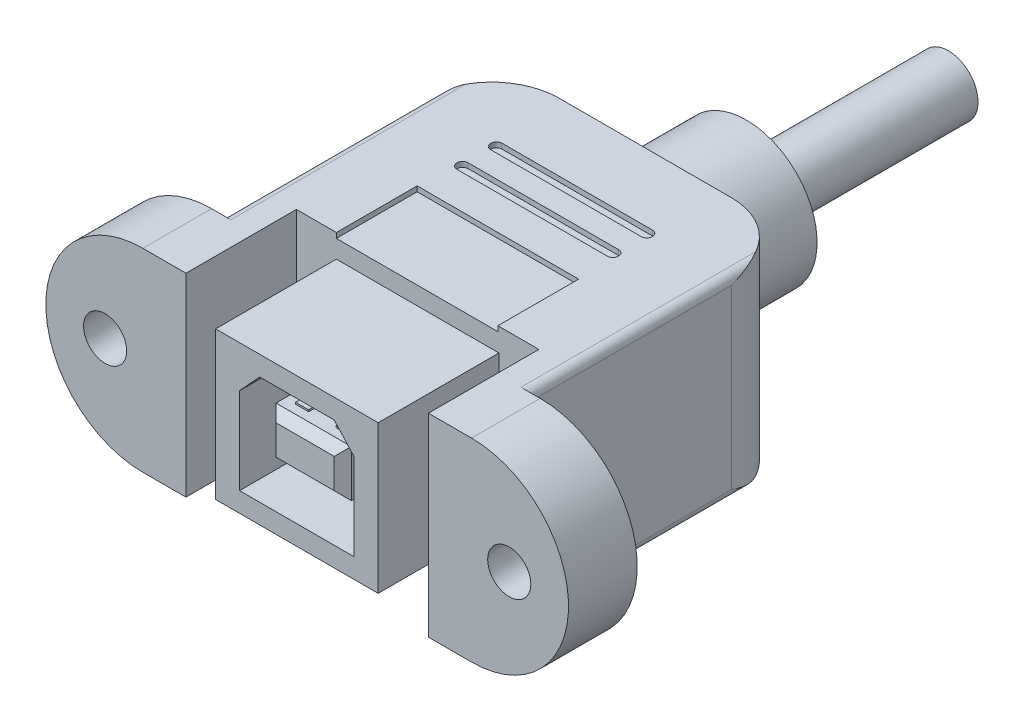
SolidWorks part; units mm, degrees
ref_plane "Front Plane" through (0, 0, 0) normal (0, 0, 1) x (1, 0, 0)
ref_plane "Top Plane" through (0, 0, 0) normal (0, 1, 0) x (1, 0, 0)
ref_plane "Right Plane" through (0, 0, 0) normal (1, 0, 0) x (0, 0, -1)
sketch "Sketch1" plane through (0, 0, 0) normal (0, 0, 1) x (1, 0, 0)
  line L0 (-19.4, 0) -> (-15, 0) construction
  line L1 (-12.2, -7.2) -> (12.2, -7.2)
  line L2 (-15, 0) -> (0, 0) construction
  line L3 (-12.2, 7.2) -> (12.2, 7.2)
  line L4 (0, 0) -> (15, 0) construction
  line L5 (0, 7.2) -> (0, 0) construction
  line L6 (15, 0) -> (19.4, 0) construction
  line L7 (0, 0) -> (0, -7.2) construction
  arc A0 (-12.2, -7.2) -> (-12.2, 7.2) centre (-12.2, 0) cw
  arc A1 (12.2, 7.2) -> (12.2, -7.2) centre (12.2, 0) cw
  circle A6 centre (-15, 0) radius 1.6
  circle A7 centre (15, 0) radius 1.6
  point P1 (20.1168, 14.45)
  point P3 (20.1168, 0)
  point P28 (0, 14.45)
  dimension "D3" = 3.2
  dimension "D7" = 30
  dimension "D1" = 14.4
  dimension "D2" = 38.8
extrude "Boss-Extrude1" add sketch "Sketch1" along normal blind 5.1
sketch "Sketch2" plane through (0, 0, 0) normal (0, 0, -1) x (-1, 0, 0)
  line L0 (12.2, -7.2) -> (-12.2, -7.2) construction
  line L1 (-10.765, 7.2) -> (10.765, 7.2)
  line L2 (-11.4, 6.565) -> (-11.4, -6.565)
  line L3 (-10.765, -7.2) -> (10.765, -7.2)
  line L4 (11.4, 6.565) -> (11.4, -6.565)
  line L5 (-12.2, 7.2) -> (12.2, 7.2) construction
  line L6 (-11.4, 0) -> (0, 0) construction
  line L7 (0, 0) -> (11.4, 0) construction
  arc A0 (-11.4, -6.565) -> (-10.765, -7.2) centre (-10.765, -6.565) ccw
  arc A1 (10.765, -7.2) -> (11.4, -6.565) centre (10.765, -6.565) ccw
  arc A2 (10.765, 7.2) -> (11.4, 6.565) centre (10.765, 6.565) cw
  arc A3 (-10.765, 7.2) -> (-11.4, 6.565) centre (-10.765, 6.565) ccw
  point P9 (0, 0)
  dimension "D1" = 0.635
  dimension "D2" = 22.8
extrude "Boss-Extrude2" add sketch "Sketch2" along normal blind 20
sketch "Sketch3" plane through (0, 0, -20) normal (0, 0, -1) x (-1, 0, 0)
  circle A0 centre (0, 0) radius 5.25
  dimension "D1" = 10.5
extrude "Boss-Extrude3" add sketch "Sketch3" along normal blind 7.5
sketch "Sketch4" plane through (0, 0, -27.5) normal (0, 0, -1) x (-1, 0, 0)
  circle A0 centre (0, 0) radius 2.2
  dimension "D1" = 4.4
extrude "Boss-Extrude4" add sketch "Sketch4" along normal blind 15
sketch "Sketch11" plane through (0, 7.2, 0) normal (0, 1, 0) x (1, 0, 0)
  line L0 (12.2, -5.1) -> (-12.2, -5.1) construction
  line L1 (-9, -5.1) -> (9, -5.1)
  line L2 (-9, -5.1) -> (-9, 3.1)
  line L3 (-9, 3.1) -> (9, 3.1)
  line L4 (9, -5.1) -> (9, 3.1)
  line L5 (0, 3.1) -> (0, 0) construction
  dimension "D1" = 18
  dimension "D2" = 8.2
extrude "Cut-Extrude3" cut sketch "Sketch11" against normal through all
sketch "Sketch5" plane through (0, 0, 5.1) normal (0, 0, 1) x (1, 0, 0)
  line L0 (0, 0) -> (0, 5.4864) construction
  line L1 (-6.0325, 5.4864) -> (6.0325, 5.4864)
  line L2 (-6.0325, 5.4864) -> (-6.0325, -5.4864)
  line L3 (-6.0325, -5.4864) -> (6.0325, -5.4864)
  line L4 (6.0325, 5.4864) -> (6.0325, -5.4864)
  circle A0 centre (15, 0) radius 1.6 construction
  dimension "D2" = 5.4864
  dimension "D3" = 10.9728
  dimension "D4" = 12.065
extrude "Boss-Extrude5" add sketch "Sketch5" along normal blind 0.762
sketch "Sketch12" plane through (0, 0, -3.1) normal (0, 0, 1) x (1, 0, 0)
  line L1 (-6.0325, 5.4864) -> (6.0325, 5.4864)
  line L2 (-6.0325, 5.4864) -> (-6.0325, -5.4864)
  line L3 (-6.0325, -5.4864) -> (6.0325, -5.4864)
  line L4 (6.0325, 5.4864) -> (6.0325, -5.4864)
extrude "Boss-Extrude9" add sketch "Sketch12" along normal up to surface (8.2 mm away) up to face at (0, 0, 5.1)
sketch "Sketch6" plane through (0, 0, 5.862) normal (0, 0, 1) x (1, 0, 0)
  line L0 (-4.2545, 2.4003) -> (-4.2545, -4.0259)
  line L5 (-4.2545, -4.0259) -> (4.2545, -4.0259)
  line L6 (4.2545, 2.4003) -> (4.2545, -4.0259)
  line L8 (-2.7686, 4.0259) -> (2.7686, 4.0259)
  line L9 (0, 4.0259) -> (0, -4.0259) construction
  line L13 (-2.7686, 4.0259) -> (-4.2545, 2.4003)
  line L18 (2.7686, 4.0259) -> (4.2545, 2.4003)
  point P6 (5.8039, 10.5664)
  point P9 (14.3129, 10.5664)
  point P10 (4.0259, 11.2014)
  point P11 (16.0909, 11.2014)
  point P14 (7.2898, 12.3444)
  point P15 (7.2898, 1.3716)
  point P16 (12.827, 12.3444)
  point P17 (12.827, 1.3716)
  point P18 (4.0259, 9.5758)
  point P19 (16.0909, 9.5758)
  dimension "D1" = 8.0518
  dimension "D2" = 8.509
  dimension "D3" = 5.5372
  dimension "D4" = 8.509
  dimension "D5" = 1.4859
  dimension "D6" = 1.6256
extrude "Cut-Extrude1" cut sketch "Sketch6" against normal blind 8.89
sketch "Sketch7" plane through (0, 0, -3.028) normal (0, 0, 1) x (1, 0, 0)
  line L0 (0, 4.0259) -> (0, -4.0259) construction
  line L1 (2.7686, 4.0259) -> (-2.7686, 4.0259) construction
  line L2 (-4.2545, -4.0259) -> (4.2545, -4.0259) construction
  line L3 (4.2545, -0.8128) -> (-4.2545, -0.8128) construction
  line L4 (4.2545, -4.0259) -> (4.2545, 2.4003) construction
  line L5 (-4.2545, 2.4003) -> (-4.2545, -4.0259) construction
  line L6 (-2.7686, 1.7399) -> (-2.7686, -1.7399)
  line L7 (2.8194, 1.7399) -> (2.8194, -1.7399)
  line L8 (-4.2545, -4.0259) -> (4.2545, -4.0259) construction
  line L9 (-2.7686, 4.0259) -> (2.8194, 4.0259) construction
  line L10 (-2.7686, -1.7399) -> (2.8194, -1.7399)
  line L11 (-2.7686, 1.7399) -> (2.8194, 1.7399)
  line L12 (-2.7686, 0) -> (0, 0) construction
  line L13 (-2.7686, 4.0259) -> (-2.7686, -4.0259) construction
  line L14 (2.8194, 4.0259) -> (2.8194, -4.0259) construction
  line L15 (-4.2545, -1.7399) -> (4.2545, -1.7399) construction
  dimension "D1" = 3.4798
  dimension "D2" = 5.588
extrude "Boss-Extrude6" add sketch "Sketch7" along normal blind 8.3058
chamfer "Chamfer1" distance 0.635 angle 45 4 edges at (-2.7686, 0, 5.2778) (0.0254, -1.7399, 5.2778) (2.8194, 0, 5.2778) (0.0254, 1.7399, 5.2778)
sketch "Sketch8" plane through (0, 1.7399, 0) normal (0, 1, 0) x (1, 0, 0)
  line L0 (2.8194, 3.028) -> (-2.7686, 3.028) construction
  line L1 (-1.9633, 3.028) -> (-0.9959, 3.028)
  line L2 (-1.9633, 3.028) -> (-1.9633, -3.9955)
  line L3 (-1.9633, -3.9955) -> (-0.9959, -3.9955)
  line L4 (-0.9959, 3.028) -> (-0.9959, -3.9955)
  line L5 (0.0254, -5.2778) -> (0.0254, -3.2159) construction
  line L6 (1.0467, 3.028) -> (1.0467, -3.9955)
  line L7 (2.0141, -3.9955) -> (1.0467, -3.9955)
  line L8 (2.0141, 3.028) -> (2.0141, -3.9955)
  line L9 (2.0141, 3.028) -> (1.0467, 3.028)
  line L10 (2.1844, -5.2778) -> (-2.1336, -5.2778) construction
  dimension "D1" = 0.9674
  dimension "D2" = 2.0425
  dimension "D3" = 7.0235
extrude "Boss-Extrude7" add sketch "Sketch8" along normal blind 0.127
ref_plane "Plane1" through (0, 0, 0) normal (0, -1, 0) x (1, 0, 0)
mirror "Mirror1" about plane through (0, 0, 0) normal (0, -1, 0) of "Boss-Extrude7"
sketch "Sketch9" plane through (0, 7.2, 0) normal (0, 1, 0) x (1, 0, 0)
  line L0 (-0.0381, 14.149) -> (-0.0381, 11.6344) construction
  line L1 (-6.0325, 9.0944) -> (5.9563, 9.0944)
  line L2 (-6.0325, 9.0944) -> (-6.0325, 3.1)
  line L3 (-6.0325, 3.1) -> (5.9563, 3.1)
  line L4 (5.9563, 9.0944) -> (5.9563, 3.1)
  line L5 (-5.6261, 12.4726) -> (5.5499, 12.4726)
  line L6 (-6.0325, 12.0662) -> (-6.0325, 12.0408)
  line L7 (-5.6261, 11.6344) -> (5.5499, 11.6344)
  line L8 (5.9563, 12.0662) -> (5.9563, 12.0408)
  line L9 (-5.6261, 14.9872) -> (5.5499, 14.9872)
  line L10 (-6.0325, 14.5808) -> (-6.0325, 14.5554)
  line L11 (-5.6261, 14.149) -> (5.5499, 14.149)
  line L12 (5.9563, 14.5808) -> (5.9563, 14.5554)
  line L13 (-0.0381, 11.6344) -> (-0.0381, 9.0944) construction
  line L14 (9, 3.1) -> (-9, 3.1) construction
  line L15 (6.0325, 3.1) -> (-6.0325, 3.1) construction
  arc A0 (5.5499, 14.9872) -> (5.9563, 14.5808) centre (5.5499, 14.5808) cw
  arc A1 (5.5499, 14.149) -> (5.9563, 14.5554) centre (5.5499, 14.5554) ccw
  arc A2 (5.5499, 12.4726) -> (5.9563, 12.0662) centre (5.5499, 12.0662) cw
  arc A3 (5.5499, 11.6344) -> (5.9563, 12.0408) centre (5.5499, 12.0408) ccw
  arc A4 (-6.0325, 12.0408) -> (-5.6261, 11.6344) centre (-5.6261, 12.0408) ccw
  arc A5 (-5.6261, 12.4726) -> (-6.0325, 12.0662) centre (-5.6261, 12.0662) ccw
  arc A6 (-6.0325, 14.5554) -> (-5.6261, 14.149) centre (-5.6261, 14.5554) ccw
  arc A7 (-5.6261, 14.9872) -> (-6.0325, 14.5808) centre (-5.6261, 14.5808) ccw
  point P20 (5.9563, 14.149)
  point P25 (5.9563, 11.6344)
  point P28 (-6.0325, 11.6344)
  point P33 (-6.0325, 14.149)
  point P36 (-6.0325, 14.9872)
  dimension "D11" = 0.4064
  dimension "D2" = 5.9944
  dimension "D3" = 2.54
  dimension "D4" = 0.8382
  dimension "D5" = 0.8382
  dimension "D6" = 1.6764
  dimension "D8" = 11.9888
  dimension "D9" = 11.9888
  dimension "D10" = 11.9888
extrude "Cut-Extrude2" cut sketch "Sketch9" against normal blind 0.381
ref_plane "Plane2" through (0, 0, 0) normal (0, 1, 0) x (-1, 0, 0)
mirror "Mirror3" about plane through (0, 0, 0) normal (0, 1, 0) of "Cut-Extrude2"
sketch "Sketch10" plane through (0, 6.819, 0) normal (0, 1, 0) x (1, 0, 0)
  line L0 (4.3979, 2.5403) -> (5.4832, 1.9137)
  line L1 (6.4231, 3.7935) -> (6.4231, 5.0467)
  line L2 (6.4231, 3.7935) -> (7.6763, 3.7935)
  line L3 (7.6763, 3.7935) -> (7.6763, 4.2133)
  line L4 (6.4231, 5.0467) -> (7.6763, 5.0467)
  line L5 (5.4832, 1.9137) -> (5.4832, 2.3335)
  line L6 (5.4832, 2.3335) -> (12.1084, 2.3335)
  line L7 (12.1084, 2.3335) -> (11.0911, 1.2589)
  line L8 (4.3979, 2.5403) -> (5.4832, 3.1669)
  line L9 (5.4832, 3.1669) -> (5.4832, 2.7471)
  line L10 (5.4832, 2.7471) -> (10.3289, 2.7471)
  line L11 (10.3289, 2.7471) -> (9.3116, 3.8217)
  line L12 (7.6763, 4.2133) -> (8.4015, 4.2133)
  line L13 (7.6763, 4.6269) -> (8.4015, 4.6269)
  line L14 (7.6763, 4.6269) -> (7.6763, 5.0467)
  line L15 (9.2078, 0.8673) -> (10.1811, 0.8673)
  line L16 (9.2078, 0.4537) -> (10.1811, 0.4537)
  line L17 (12.6779, 2.3335) -> (13.4367, 2.3335)
  line L18 (10.8983, 2.7471) -> (13.4367, 2.7471)
  line L19 (12.6779, 2.3335) -> (11.3915, 0.9746)
  line L20 (10.8983, 2.7471) -> (9.6119, 4.106)
  arc A0 (13.4367, 2.3335) -> (13.4367, 2.7471) centre (14.4625, 2.5403) ccw
  arc A1 (9.2078, 0.8673) -> (9.2078, 0.4537) centre (8.6162, 0.6605) ccw
  arc A2 (11.0911, 1.2589) -> (10.1811, 0.8673) centre (10.1811, 2.1205) cw
  arc A3 (11.3915, 0.9746) -> (10.1811, 0.4537) centre (10.1811, 2.1205) cw
  arc A4 (9.3116, 3.8217) -> (8.4015, 4.2133) centre (8.4015, 2.9601) ccw
  arc A5 (9.6119, 4.106) -> (8.4015, 4.6269) centre (8.4015, 2.9601) ccw
extrude "Boss-Extrude8" [suppressed] add sketch "Sketch10" along normal blind 0.381
fillet "Fillet1" radius 5 2 edges at (11.4, 0, -20) (-11.4, 0, -20) tangent propagation no
